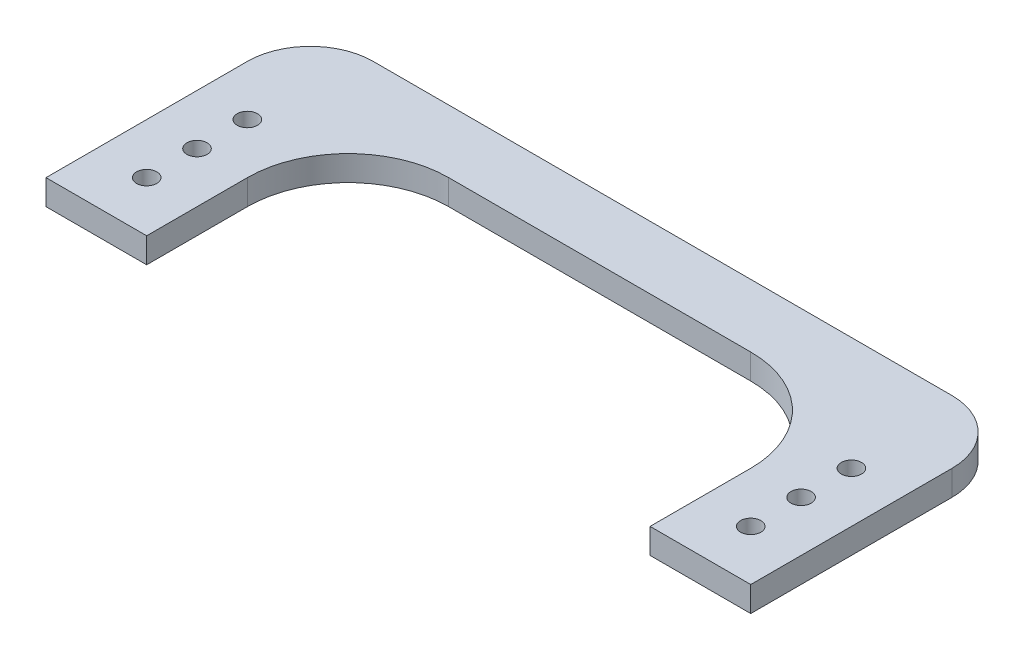
SolidWorks part; units mm, degrees
material "6061-T6 (SS)"
ref_plane "Front" through (0, 0, 0) normal (0, 0, 1) x (1, 0, 0)
ref_plane "Top" through (0, 0, 0) normal (0, 1, 0) x (1, 0, 0)
ref_plane "Right" through (0, 0, 0) normal (1, 0, 0) x (0, 0, -1)
sketch "Sketch1" plane through (0, 0, 0) normal (0, 1, 0) x (1, 0, 0)
  line L0 (-63.5, -25.4) -> (-63.5, 0)
  line L1 (63.5, 0) -> (63.5, -25.4)
  line L2 (63.5, -25.4) -> (88.9, -25.4)
  line L3 (0, 0) -> (0, -66.2098) construction
  line L4 (-63.5, -25.4) -> (-88.9, -25.4)
  line L5 (-88.9, -25.4) -> (-88.9, 25.4)
  line L6 (88.9, 25.4) -> (88.9, -25.4)
  line L8 (-38.1, 25.4) -> (38.1, 25.4)
  line L12 (73.025, 41.275) -> (-73.025, 41.275)
  line L14 (88.9, 6.8059) -> (88.9, -25.4) construction
  line L15 (-88.9, -25.4) -> (-88.9, 6.8059) construction
  arc A6 (47.628, 9.9217) -> (63.5, 0) centre (43.0476, -15.0619) cw construction
  arc A7 (-88.9, 6.8059) -> (-56.1751, 50.962) centre (95.1959, -95.4263) cw construction
  arc A8 (-56.1751, 50.962) -> (52.2083, 34.9053) centre (-236.3524, -1539.0619) cw construction
  arc A9 (52.2083, 34.9053) -> (88.9, 6.8059) centre (43.0476, -15.0619) cw construction
  arc A10 (-63.5, 0) -> (-46.1472, 24.2094) centre (95.1959, -95.4263) cw construction
  arc A11 (-46.1472, 24.2094) -> (47.628, 9.9217) centre (-236.3524, -1539.0619) cw construction
  arc A13 (88.9, 25.4) -> (73.025, 41.275) centre (73.025, 25.4) ccw
  arc A15 (-73.025, 41.275) -> (-88.9, 25.4) centre (-73.025, 25.4) ccw
  arc A16 (38.1, 25.4) -> (63.5, 0) centre (38.1, 0) cw
  arc A17 (-63.5, 0) -> (-38.1, 25.4) centre (-38.1, 0) cw
  dimension "D9" = 25.4
  dimension "D1" = 127
  dimension "D2" = 50.8
  dimension "D6" = 15.875
  dimension "D3" = 25.4
extrude "Boss-Extrude1" add sketch "Sketch1" along normal blind 6.35
hole_wizard "#10 Clearance Hole1" positions "Sketch2" profile "Sketch3" hole size "#10" standard "ANSI Inch" end condition through all
sketch "Sketch2" plane through (0, 6.35, 0) normal (0, 1, 0) x (1, 0, 0)
  line L3 (-88.9, -25.4) -> (-76.2, -12.7) construction
  line L4 (-76.2, -12.7) -> (-76.2, 0) construction
  line L5 (-76.2, 0) -> (-76.2, 12.7) construction
  line L6 (-76.2, 12.7) -> (-63.5, 25.4) construction
  line L8 (0, 0) -> (0, -50.8) construction
  line L9 (-63.5, -25.4) -> (-63.5, 0) construction
  line L10 (-38.1, 25.4) -> (38.1, 25.4) construction
  point P0 (-76.2, -12.7)
  point P2 (-76.2, 0)
  point P4 (-76.2, 12.7)
  point P29 (76.2, 12.7)
  point P30 (76.2, 0)
  point P31 (76.2, -12.7)
  dimension "D1" = 12.7
sketch "Sketch3" plane through (-76.2, 6.35, 12.7) normal (1, 0, 0) x (0, 0, 1)
  line L0 (0, 0) -> (0, 6.35)
  line L1 (0, 6.35) -> (2.5527, 6.35)
  line L2 (2.5527, 6.35) -> (2.5527, 0)
  line L5 (2.5527, 0) -> (0, 0)
  line L11 (0, -6.35) -> (0, 107.95) construction
  dimension "Thru Hole Dia." = 5.1054
  dimension "Thru Hole Depth" = 6.35
